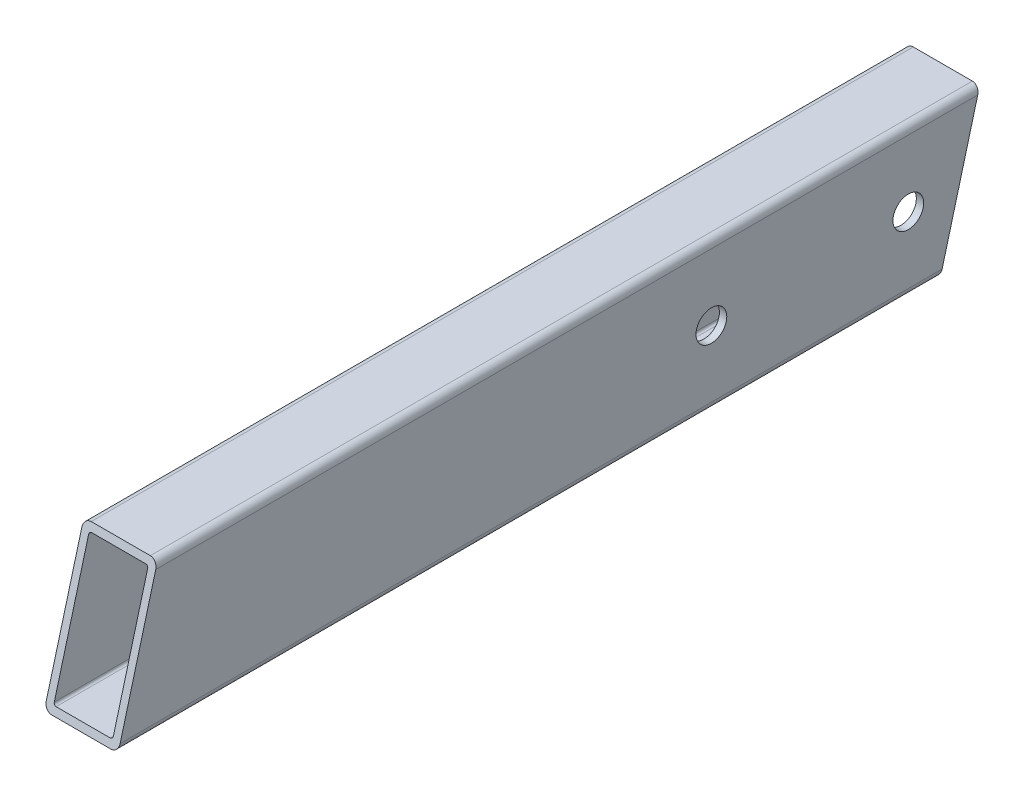
SolidWorks part; units mm, degrees
material "1.0114 (S235J0)"
ref_plane "Płaszczyzna przednia" through (0, 0, 0) normal (0, 0, 1) x (1, 0, 0)
ref_plane "Płaszczyzna górna" through (0, 0, 0) normal (0, 1, 0) x (1, 0, 0)
ref_plane "Płaszczyzna prawa" through (0, 0, 0) normal (1, 0, 0) x (0, 0, -1)
sketch "Szkic1" plane through (0, 0, 0) normal (0, 0, 1) x (1, 0, 0)
  line L0 (-7.1969, 27) -> (14.8031, 27)
  line L1 (-8.1969, -30) -> (15.8031, -30)
  line L2 (-11.1969, -27) -> (-11.1969, 27)
  line L3 (-8.1969, 30) -> (15.8031, 30)
  line L4 (18.8031, -27) -> (18.8031, 27)
  line L5 (15.8031, -26) -> (15.8031, 26)
  line L6 (-7.1969, -27) -> (14.8031, -27)
  line L7 (-8.1969, -26) -> (-8.1969, 26)
  line L8 (-11.1969, 30) -> (18.8031, 30) construction
  line L9 (18.8031, -30) -> (18.8031, 30) construction
  line L10 (-11.1969, -30) -> (18.8031, -30) construction
  line L11 (-11.1969, -30) -> (-11.1969, 30) construction
  line L12 (-8.1969, 27) -> (15.8031, 27) construction
  line L13 (15.8031, -27) -> (15.8031, 27) construction
  line L14 (-8.1969, -27) -> (15.8031, -27) construction
  line L15 (-8.1969, -27) -> (-8.1969, 27) construction
  line L16 (55, 0) -> (-55, 0) construction
  arc A0 (15.8031, 30) -> (18.8031, 27) centre (15.8031, 27) cw
  arc A1 (18.8031, -27) -> (15.8031, -30) centre (15.8031, -27) cw
  arc A2 (-8.1969, -30) -> (-11.1969, -27) centre (-8.1969, -27) cw
  arc A3 (-11.1969, 27) -> (-8.1969, 30) centre (-8.1969, 27) cw
  arc A4 (14.8031, 27) -> (15.8031, 26) centre (14.8031, 26) cw
  arc A5 (15.8031, -26) -> (14.8031, -27) centre (14.8031, -26) cw
  arc A6 (-7.1969, -27) -> (-8.1969, -26) centre (-7.1969, -26) cw
  arc A7 (-8.1969, 26) -> (-7.1969, 27) centre (-7.1969, 26) cw
  point P4 (-11.1969, 0)
  point P12 (15, 0)
  dimension "D4" = 3
  dimension "D1" = 1
  dimension "D2" = 30
  dimension "D5" = 60
  dimension "D3" = 3
extrude "Dodanie-wyciągnięcie1" add sketch "Szkic1" against normal blind 350
sketch "Szkic2" plane through (0, 0, 0) normal (1, 0, 0) x (0, 0, -1)
  line L2 (0, -30) -> (16.077, 30)
  line L4 (350, 30) -> (0, 30) construction
  line L5 (16.077, 30) -> (0, 30)
  line L6 (0, 30) -> (0, -30)
  line L7 (350, 30) -> (333.923, -30)
  line L8 (350, -30) -> (0, -30) construction
  line L9 (333.923, -30) -> (350, -30)
  line L10 (350, -30) -> (350, 30)
  dimension "D1" = 15
  dimension "D2" = 15
extrude "Wytnij-wyciągnięcie1" cut sketch "Szkic2" against normal blind 50 and the other way blind 52
sketch "Szkic3" plane through (18.8031, 0, 0) normal (1, 0, 0) x (0, 0, -1)
  line L3 (16.5, 0) -> (-16.5, 0) construction
  line L6 (0, 73.9155) -> (0, -73.9155) construction
  circle A0 centre (321, 0) radius 6.25
  circle A1 centre (241, 0) radius 6.25
  point P6 (221.3076, 140.8098)
  point P7 (0, 0)
  point P8 (0, 0)
  dimension "D2" = 12.5
  dimension "D1" = 80
  dimension "D3" = 321
extrude "Wytnij-wyciągnięcie2" cut sketch "Szkic3" against normal up to surface (30 mm away) up to face at (-11.1969, 0, -175)
